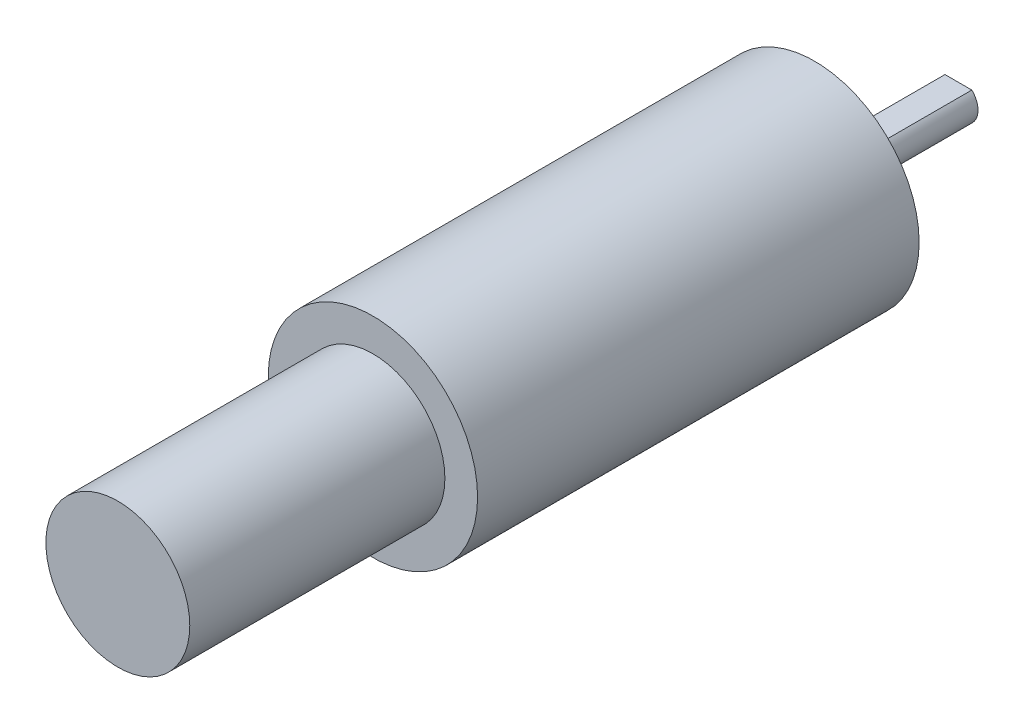
SolidWorks part; units mm, degrees
ref_plane "Front Plane" through (0, 0, 0) normal (0, 0, 1) x (1, 0, 0)
ref_plane "Top Plane" through (0, 0, 0) normal (0, 1, 0) x (1, 0, 0)
ref_plane "Right Plane" through (0, 0, 0) normal (1, 0, 0) x (0, 0, -1)
sketch "Sketch1" plane through (0, 0, 0) normal (0, 0, 1) x (1, 0, 0)
  circle A0 centre (0, 0) radius 16
  dimension "D1" = 32
extrude "Boss-Extrude1" add sketch "Sketch1" along normal blind 67.5
sketch "Sketch2" plane through (0, 0, 0) normal (0, 0, -1) x (-1, 0, 0)
  circle A0 centre (0, 0) radius 9
  dimension "D1" = 18
extrude "Boss-Extrude2" add sketch "Sketch2" along normal blind 1
sketch "Sketch3" plane through (0, 0, -1) normal (0, 0, -1) x (-1, 0, 0)
  circle A0 centre (0, 0) radius 3
  dimension "D1" = 6
extrude "Boss-Extrude3" add sketch "Sketch3" along normal blind 21
sketch "Sketch4" plane through (0, 0, -22) normal (0, 0, -1) x (-1, 0, 0)
  line L0 (-3.1619, 2.1873) -> (3.4651, 2.1873)
  line L1 (3.4651, 2.1873) -> (3.4651, 5.6091)
  line L2 (3.4651, 5.6091) -> (-3.1619, 2.1873)
extrude "Cut-Extrude1" cut sketch "Sketch4" against normal blind 17.698
sketch "Sketch5" plane through (0, 0, 67.5) normal (0, 0, 1) x (1, 0, 0)
  circle A0 centre (0, 0) radius 11
  dimension "D1" = 22
extrude "Boss-Extrude4" add sketch "Sketch5" along normal blind 39
hole_wizard "M3x0.5 Tapped Hole1" positions "Sketch7" profile "Sketch8" tap size "M3x0.5" standard "Ansi Metric"
sketch "Sketch7" plane through (0, 0, 0) normal (0, 0, -1) x (-1, 0, 0)
  point P0 (0, 13)
  dimension "D1" = 13
sketch "Sketch8" plane through (0, 13, 0) normal (1, 0, 0) x (0, 1, 0)
  line L0 (0, 0) -> (0, 8.3711)
  line L1 (0, 8.3711) -> (1.25, 7.62)
  line L2 (1.25, 7.62) -> (1.25, 0)
  line L5 (1.25, 0) -> (0, 0)
  line L10 (0, 8.3711) -> (-1.25, 7.62) construction
  line L11 (0, -6.35) -> (0, 107.95) construction
  dimension "Tap Drill Dia." = 2.5
  dimension "Tap Drill Depth" = 7.62
  dimension "Drill Angle" = 118
pattern_circular "CirPattern1" count 4 over 360 about axis through (0, 0, 67.5) along (0, 0, -1) of "M3x0.5 Tapped Hole1"
